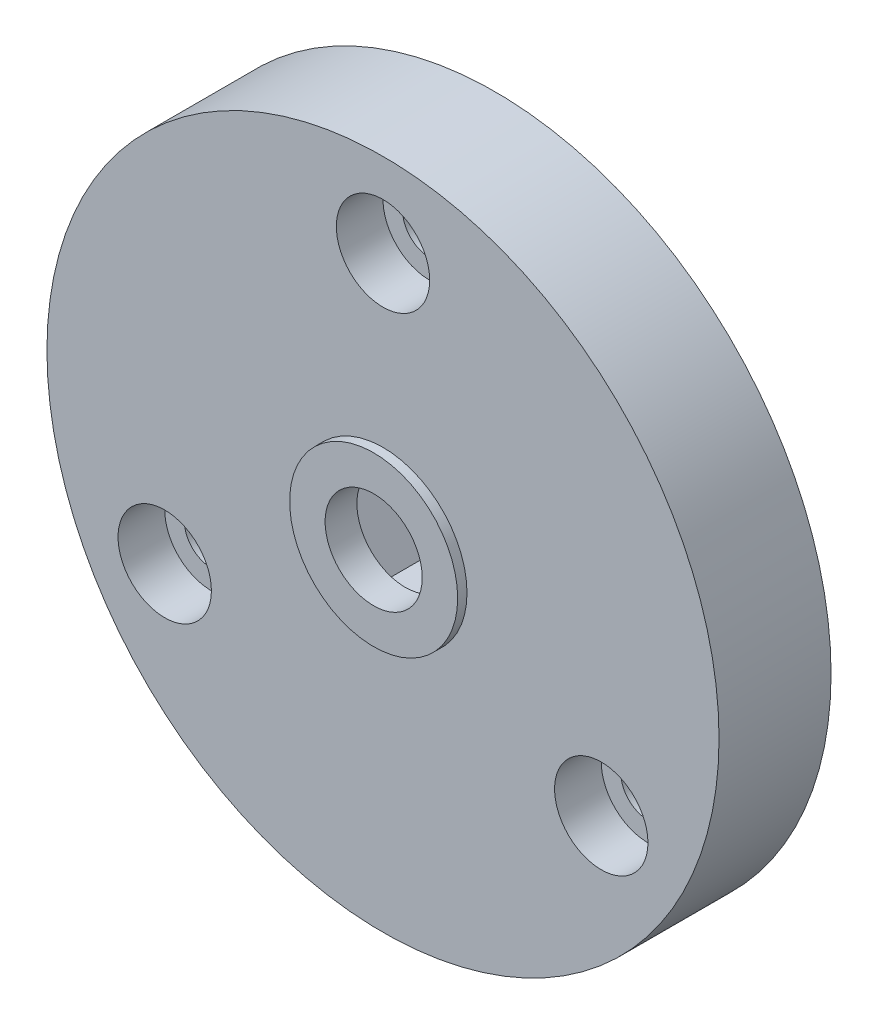
SolidWorks part; units mm, degrees
ref_plane "Front Plane" through (0, 0, 0) normal (0, 0, 1) x (1, 0, 0)
ref_plane "Top Plane" through (0, 0, 0) normal (0, 1, 0) x (1, 0, 0)
ref_plane "Right Plane" through (0, 0, 0) normal (1, 0, 0) x (0, 0, -1)
ref_plane "Plane1" through (0, 0, 322) normal (0, 0, 1) x (1, 0, 0)
sketch "Sketch1" plane through (0, 0, 322) normal (0, 0, 1) x (1, 0, 0)
  circle A0 centre (300, 300) radius 18
  circle A1 centre (300, 300) radius 2.6
  circle A2 centre (300, 313.5) radius 1.45
  circle A3 centre (288.3087, 293.25) radius 1.45
  circle A4 centre (311.6913, 293.25) radius 1.45
extrude "Boss-Extrude1" add sketch "Sketch1" along normal blind 6
ref_plane "Plane2" through (0, 0, 325.5) normal (0, 0, 1) x (1, 0, 0)
sketch "Sketch2" plane through (0, 0, 325.5) normal (0, 0, 1) x (1, 0, 0)
  circle A0 centre (300, 313.5) radius 2.5
  circle A1 centre (288.3087, 293.25) radius 2.5
  circle A2 centre (311.6913, 293.25) radius 2.5
extrude "Cut-Extrude1" cut sketch "Sketch2" along normal blind 2.5
sketch "Sketch3" plane through (0, 0, 322) normal (0, 0, 1) x (1, 0, 0)
  circle A0 centre (300, 300) radius 7.6
extrude "Cut-Extrude2" cut sketch "Sketch3" along normal blind 1.2
ref_plane "Plane3" through (0, 0, 323.2) normal (0, 0, 1) x (1, 0, 0)
sketch "Sketch4" plane through (0, 0, 323.2) normal (0, 0, 1) x (1, 0, 0)
  line L0 (304.7343, 300) -> (302.3671, 304.1)
  line L1 (302.3671, 304.1) -> (297.6329, 304.1)
  line L2 (297.6329, 304.1) -> (295.2657, 300)
  line L3 (295.2657, 300) -> (297.6329, 295.9)
  line L4 (297.6329, 295.9) -> (302.3671, 295.9)
  line L5 (302.3671, 295.9) -> (304.7343, 300)
extrude "Cut-Extrude3" cut sketch "Sketch4" along normal blind 3.6
ref_plane "Plane4" through (0, 0, 328) normal (0, 0, 1) x (1, 0, 0)
sketch "Sketch5" plane through (0, 0, 328) normal (0, 0, 1) x (1, 0, 0)
  circle A0 centre (300, 300) radius 4.5
  circle A1 centre (300, 300) radius 2.6
extrude "Boss-Extrude2" add sketch "Sketch5" along normal blind 0.5
ref_plane "Plane5" through (300, 0, 0) normal (1, 0, 0) x (0, 0, -1)
ref_plane "Plane6" through (0, 300, 0) normal (0, 1, 0) x (1, 0, 0)
ref_axis "HIP_AXIS" through (300, 300, 328.825) along (0, 0, -1)
